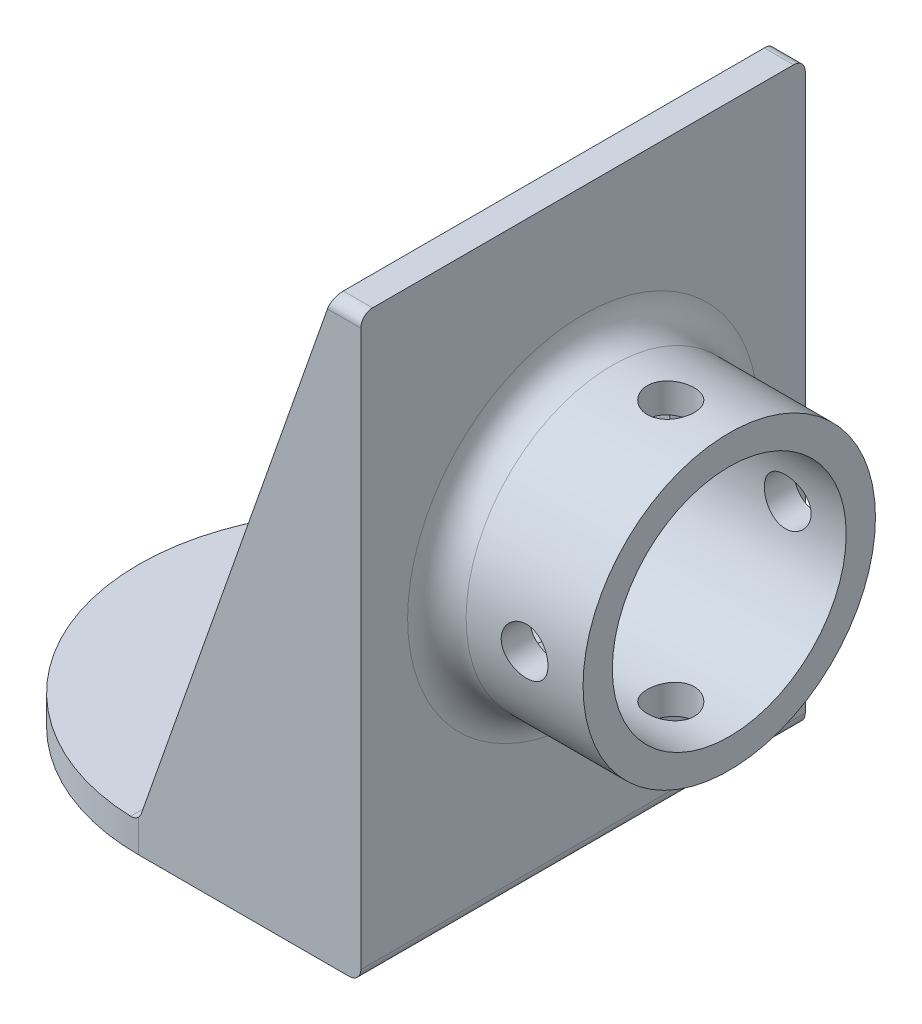
SolidWorks part; units mm, degrees
ref_plane "Спереди" through (0, 0, 0) normal (0, 0, 1) x (1, 0, 0)
ref_plane "Сверху" through (0, 0, 0) normal (0, 1, 0) x (1, 0, 0)
ref_plane "Справа" through (0, 0, 0) normal (1, 0, 0) x (0, 0, -1)
sketch "Эскиз3" plane through (0, 0, 0) normal (0, 0, 1) x (1, 0, 0)
  line L1 (76, 0) -> (0, 0)
  line L3 (71, 5) -> (0, 5)
  line L4 (0, 0) -> (0, 5)
  line L8 (76, 0) -> (76, 99)
  line L9 (76, 99) -> (71, 99)
  line L10 (71, 5) -> (71, 99)
  point P0 (0, 0)
  dimension "D1" = 5
  dimension "D2" = 76
  dimension "D3" = 5
  dimension "D4" = 99
extrude "Бобышка-Вытянуть1" add sketch "Эскиз3" along normal blind 76
fillet "Скругление1" radius 38 2 edges at (0, 2.5, 0) (0, 2.5, 76)
ref_plane "Плоскость7" through (0, 0, 0) normal (0, 0, -1) x (-1, 0, 0)
ref_plane "Плоскость8" through (0, 0, 76) normal (0, 0, 1) x (1, 0, 0)
sketch "Эскиз4" plane through (0, 0, 76) normal (0, 0, 1) x (1, 0, 0)
  line L0 (71, 99) -> (38, 5)
rib "Ребро1" sketch "Эскиз4" sketch "Эскиз4" thickness 5 extrusion direction parallel to sketch draft on no parameters "D1"=5
sketch "Эскиз5" plane through (0, 0, 0) normal (0, 0, -1) x (-1, 0, 0)
  line L0 (-71, 99) -> (-38, 5)
rib "Ребро2" sketch "Эскиз5" sketch "Эскиз5" thickness 5 extrusion direction parallel to sketch draft on no parameters "D1"=5
sketch "Эскиз7" plane through (0, 5, 0) normal (0, 1, 0) x (1, 0, 0)
  line L0 (38, -38) -> (20, -38) construction
  circle A0 centre (38, -38) radius 18 construction
  circle A1 centre (20, -38) radius 2.5
  circle A2 centre (38, -38) radius 18
  circle A3 centre (29, -22.4115) radius 2.5
  circle A4 centre (38, -38) radius 18
  circle A5 centre (47, -22.4115) radius 2.5
  circle A6 centre (38, -38) radius 18
  circle A7 centre (56, -38) radius 2.5
  circle A8 centre (38, -38) radius 18
  circle A9 centre (47, -53.5885) radius 2.5
  circle A10 centre (38, -38) radius 18
  circle A11 centre (29, -53.5885) radius 2.5
  dimension "D1" = 36
  dimension "D2" = 5
  dimension "D3" = 6
extrude "Вырез-Вытянуть1" cut sketch "Эскиз7" against normal blind 10 contours A1 | A3 | A5 | A7 | A9 | A11
sketch "Эскиз8" plane through (76, 0, 0) normal (1, 0, 0) x (0, 0, -1)
  line L2 (-76, 0) -> (0, 0) construction
  line L3 (0, 0) -> (0, 99) construction
  circle A12 centre (-38, 50) radius 25
  circle A13 centre (-38, 50) radius 20
  point P7 (-20.6998, 83.6617)
  dimension "D1" = 50
  dimension "D2" = 40
  dimension "D4" = 38
  dimension "D3" = 50
fillet "Скругление2" radius 2 1 edges at (76, 0, 38)
chamfer "Фаска1" distance 10 distance2 5 1 edges at (71, 5, 38) first distance on face at (71, 52, 38)
fillet "Скругление3" radius 2 2 edges at (38, 5, 73.5) (38, 5, 2.5)
fillet "Скругление4" radius 2 2 edges at (73.5, 99, 0) (73.5, 99, 76)
extrude "Вырез-Вытянуть2" cut sketch "Эскиз8" against normal blind 5 contours A13
extrude "Бобышка-Вытянуть4" add sketch "Эскиз8<6>" along normal blind 25 contours A12 | A13
sketch "Эскиз8<6>" plane through (76, 0, 0) normal (1, 0, 0) x (0, 0, -1) same geometry as "Эскиз8"
fillet "Скругление5" radius 5 1 edges at (76, 50, 63)
sketch "Эскиз13" plane through (0, 0, 0) normal (0, 0, -1) x (-1, 0, 0)
  line L0 (-101, 75) -> (-101, 25) construction
  line L1 (-101, 25) -> (-81, 25) construction
  circle A0 centre (-91, 50) radius 4
  dimension "D1" = 8
  dimension "D2" = 10
  dimension "D3" = 25
extrude "Вырез-Вытянуть3" cut sketch "Эскиз13" against normal blind 76
ref_plane "Плоскость9" through (0, 99, 0) normal (0, 1, 0) x (1, 0, 0)
sketch "Эскиз14" plane through (0, 99, 0) normal (0, 1, 0) x (1, 0, 0)
  line L0 (101, -63) -> (101, -13) construction
  line L1 (95, -63) -> (101, -63) construction
  circle A0 centre (91, -38) radius 4
  dimension "D1" = 8
  dimension "D2" = 10
  dimension "D3" = 25
extrude "Вырез-Вытянуть4" cut sketch "Эскиз14" against normal blind 76
